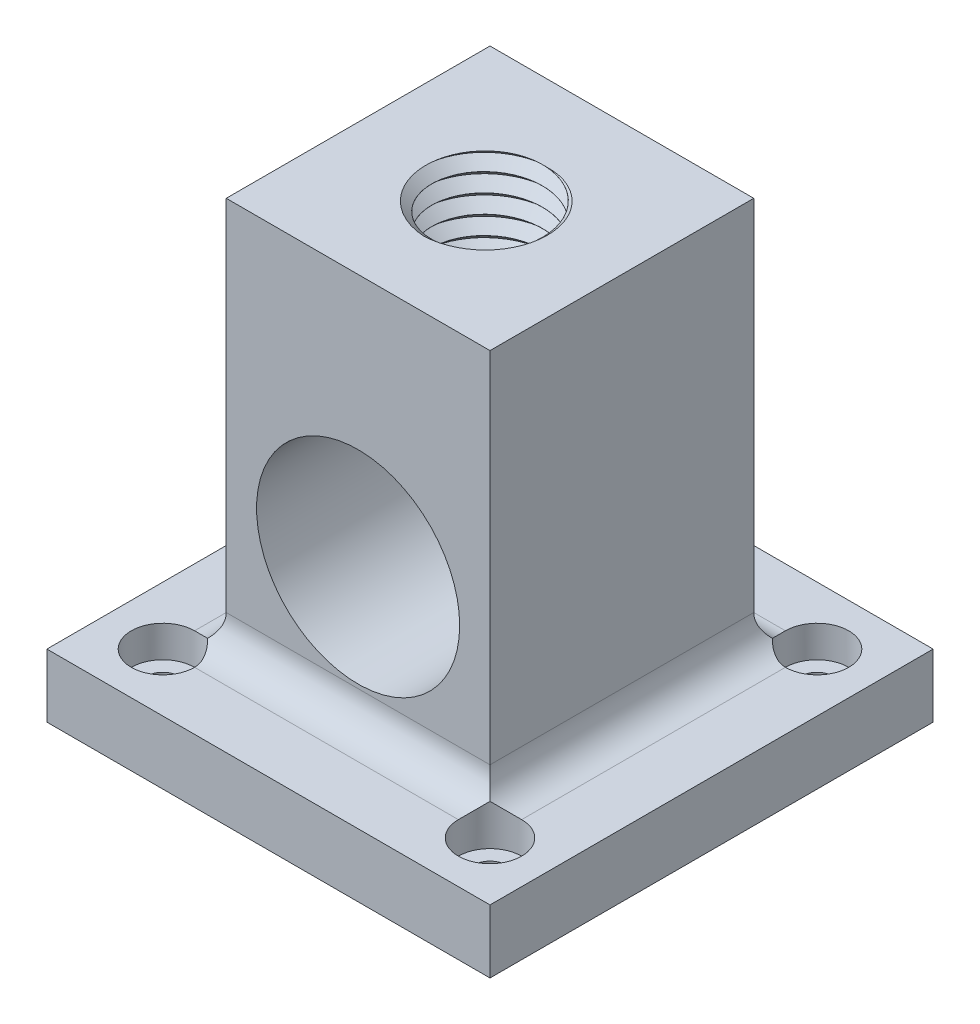
SolidWorks part; units mm, degrees
note: The reader was unsure of these and kept them because the rebuilt part matched: shared geometry of "草图1<4>", "草图4<2>".
ref_plane "前视基准面" through (0, 0, 0) normal (0, 0, 1) x (1, 0, 0)
ref_plane "上视基准面" through (0, 0, 0) normal (0, 1, 0) x (1, 0, 0)
ref_plane "右视基准面" through (0, 0, 0) normal (1, 0, 0) x (0, 0, -1)
sketch "草图1" plane through (0, 0, 0) normal (0, 1, 0) x (1, 0, 0)
  line L1 (-21, 21) -> (21, 21)
  line L2 (-21, 21) -> (-21, -21)
  line L3 (-21, -21) -> (21, -21)
  line L4 (21, 21) -> (21, -21)
  line L5 (-21, 21) -> (21, -21) construction
  line L6 (-21, -21) -> (21, 21) construction
  circle A0 centre (-15.5, 15.5) radius 1.55
  circle A1 centre (15.5, 15.5) radius 1.55
  circle A2 centre (15.5, -15.5) radius 1.55
  circle A3 centre (-15.5, -15.5) radius 1.55
  circle A4 centre (-15.5, 15.5) radius 3
  circle A5 centre (15.5, 15.5) radius 3
  circle A6 centre (15.5, -15.5) radius 3
  circle A7 centre (-15.5, -15.5) radius 3
  point P0 (0, 0)
  point P17 (0, 0)
  dimension "D2" = 3.1
  dimension "D3" = 15.5
  dimension "D5" = 6
  dimension "D1" = 42
  dimension "D4" = 4
extrude "凸台-拉伸1" add sketch "草图1" against normal blind 3 contours A7 A3 | A4 A0 | A5 A1 | A6 A2 | L4 L1 L2 L3 A7 A6 A5 A4
extrude "凸台-拉伸2" add sketch "草图1<4>" along normal blind 3 contours L4 L1 L2 L3 A7 A6 A5 A4
sketch "草图1<4>" plane through (0, 0, 0) normal (0, 1, 0) x (1, 0, 0) same geometry as "草图1"
sketch "草图2" plane through (0, 3, 0) normal (0, 1, 0) x (1, 0, 0)
  line L1 (-12.5, 12.5) -> (12.5, 12.5)
  line L2 (-12.5, 12.5) -> (-12.5, -12.5)
  line L3 (-12.5, -12.5) -> (12.5, -12.5)
  line L4 (12.5, 12.5) -> (12.5, -12.5)
  line L5 (-12.5, 12.5) -> (12.5, -12.5) construction
  line L6 (-12.5, -12.5) -> (12.5, 12.5) construction
  point P0 (0, 0)
  dimension "D1" = 25
extrude "凸台-拉伸3" add sketch "草图2" along normal blind 37
sketch "草图3" plane through (0, 0, 12.5) normal (0, 0, 1) x (1, 0, 0)
  line L0 (-12.5, 3) -> (12.5, 3) construction
  line L1 (0, 16) -> (0, 3) construction
  circle A0 centre (0, 16) radius 9.625
  point P2 (0, 3)
  dimension "D1" = 19.25
  dimension "D2" = 13
extrude "切除-拉伸1" cut sketch "草图3" against normal up to next
sketch "草图4" plane through (0, 40, 0) normal (0, 1, 0) x (1, 0, 0)
  circle A0 centre (0, 0) radius 5.25
  dimension "D1" = 10.5
extrude "切除-拉伸2" cut sketch "草图4<2>" against normal blind 12
sketch "草图4<2>" plane through (0, 40, 0) normal (0, 1, 0) x (1, 0, 0) same geometry as "草图4"
curve "螺旋线/涡状线1" pitch 1.75 height 13.125 turns 7.5
sketch "草图5" plane through (0, 0, 0) normal (1, 0, 0) x (0, 0, -1)
  line L0 (-5.25, 40) -> (-5.25, 39.13)
  line L1 (-12.5, 40) -> (12.5, 40) construction
  line L2 (-5.25, 39.13) -> (-6.25, 40)
  line L3 (-6.25, 40) -> (-5.25, 40.87)
  line L4 (-5.25, 40.87) -> (-5.25, 40)
  spline S0 degree 3 poles (-5.25, 40) (-5.25, 39.9638) (-4.9766, 39.8905) (-3.809, 39.7813) (-2.0614, 39.6719) (0, 39.5625) (2.0614, 39.4531) (3.809, 39.3438) (4.9766, 39.2344) (5.3867, 39.125) (4.9766, 39.0156) (3.809, 38.9063) (2.0614, 38.7969) (0, 38.6875) (-2.0614, 38.5781) (-3.809, 38.4688) (-4.9766, 38.3594) (-5.3867, 38.25) (-4.9766, 38.1406) (-3.809, 38.0313) (-2.0614, 37.9219) (0, 37.8125) (2.0614, 37.7031) (3.809, 37.5938) (4.9766, 37.4844) (5.3867, 37.375) (4.9766, 37.2656) (3.809, 37.1562) (2.0614, 37.0469) (0, 36.9375) (-2.0614, 36.8281) (-3.809, 36.7188) (-4.9766, 36.6094) (-5.3867, 36.5) (-4.9766, 36.3906) (-3.809, 36.2812) (-2.0614, 36.1719) (0, 36.0625) (2.0614, 35.9531) (3.809, 35.8438) (4.9766, 35.7344) (5.3867, 35.625) (4.9766, 35.5156) (3.809, 35.4062) (2.0614, 35.2969) (0, 35.1875) (-2.0614, 35.0781) (-3.809, 34.9688) (-4.9766, 34.8594) (-5.3867, 34.75) (-4.9766, 34.6406) (-3.809, 34.5312) (-2.0614, 34.4219) (0, 34.3125) (2.0614, 34.2031) (3.809, 34.0938) (4.9766, 33.9844) (5.3867, 33.875) (4.9766, 33.7656) (3.809, 33.6562) (2.0614, 33.5469) (0, 33.4375) (-2.0614, 33.3281) (-3.809, 33.2188) (-4.9766, 33.1094) (-5.3867, 33) (-4.9766, 32.8906) (-3.809, 32.7813) (-2.0614, 32.6719) (0, 32.5625) (2.0614, 32.4531) (3.809, 32.3438) (4.9766, 32.2344) (5.3867, 32.125) (4.9766, 32.0156) (3.809, 31.9062) (2.0614, 31.7969) (0, 31.6875) (-2.0614, 31.5781) (-3.809, 31.4688) (-4.9766, 31.3594) (-5.3867, 31.25) (-4.9766, 31.1406) (-3.809, 31.0312) (-2.0614, 30.9219) (0, 30.8125) (2.0614, 30.7031) (3.809, 30.5938) (4.9766, 30.4844) (5.3867, 30.375) (4.9766, 30.2656) (3.809, 30.1562) (2.0614, 30.0469) (0, 29.9375) (-2.0614, 29.8281) (-3.809, 29.7188) (-4.9766, 29.6094) (-5.3867, 29.5) (-4.9766, 29.3906) (-3.809, 29.2812) (-2.0614, 29.1719) (0, 29.0625) (2.0614, 28.9531) (3.809, 28.8437) (4.9766, 28.7344) (5.3867, 28.625) (4.9766, 28.5156) (3.809, 28.4062) (2.0614, 28.2969) (0, 28.1875) (-2.0614, 28.0781) (-3.809, 27.9687) (-4.9766, 27.8594) (-5.3867, 27.75) (-4.9766, 27.6406) (-3.809, 27.5312) (-2.0614, 27.4219) (0, 27.3125) (2.0614, 27.2031) (3.809, 27.0937) (4.9766, 26.9845) (5.25, 26.9112) (5.25, 26.875) knots 0 0 0 0 0.008333 0.016667 0.025 0.033333 0.041667 0.05 0.058333 0.066667 0.075 0.083333 0.091667 0.1 0.108333 0.116667 0.125 0.133333 0.141667 0.15 0.158333 0.166667 0.175 0.183333 0.191667 0.2 0.208333 0.216667 0.225 0.233333 0.241667 0.25 0.258333 0.266667 0.275 0.283333 0.291667 0.3 0.308333 0.316667 0.325 0.333333 0.341667 0.35 0.358333 0.366667 0.375 0.383333 0.391667 0.4 0.408333 0.416667 0.425 0.433333 0.441667 0.45 0.458333 0.466667 0.475 0.483333 0.491667 0.5 0.508333 0.516667 0.525 0.533333 0.541667 0.55 0.558333 0.566667 0.575 0.583333 0.591667 0.6 0.608333 0.616667 0.625 0.633333 0.641667 0.65 0.658333 0.666667 0.675 0.683333 0.691667 0.7 0.708333 0.716667 0.725 0.733333 0.741667 0.75 0.758333 0.766667 0.775 0.783333 0.791667 0.8 0.808333 0.816667 0.825 0.833333 0.841667 0.85 0.858333 0.866667 0.875 0.883333 0.891667 0.9 0.908333 0.916667 0.925 0.933333 0.941667 0.95 0.958333 0.966667 0.975 0.983333 0.991667 1 1 1 1 construction
  dimension "D1" = 0.87
  dimension "D2" = 1
sweep "切除-扫描1" cut profiles "草图5" path "螺旋线/涡状线1"
fillet "圆角1" radius 3 4 edges at (-12.5, 3, 0) (0, 3, 12.5) (12.5, 3, 0) (0, 3, -12.5)
